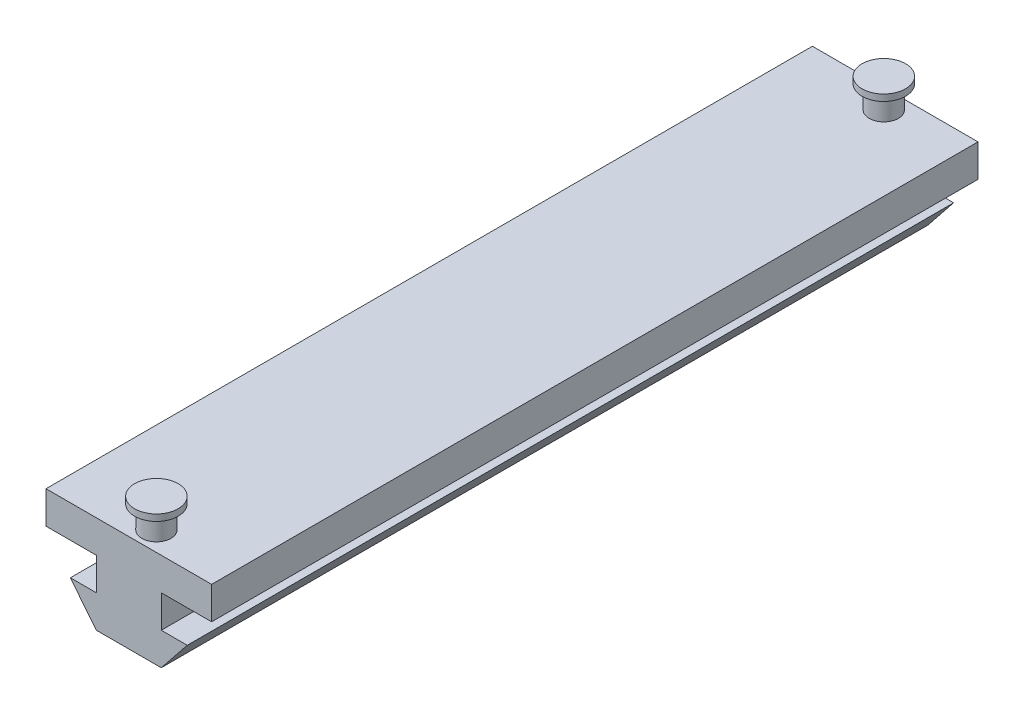
SolidWorks part; units mm, degrees
ref_plane "Front Plane" through (0, 0, 0) normal (0, 0, 1) x (1, 0, 0)
ref_plane "Top Plane" through (0, 0, 0) normal (0, 1, 0) x (1, 0, 0)
ref_plane "Right Plane" through (0, 0, 0) normal (1, 0, 0) x (0, 0, -1)
sketch "Sketch1" plane through (0, 0, 0) normal (0, 1, 0) x (1, 0, 0)
  line L1 (-12.75, -59) -> (12.75, -59)
  line L2 (-12.75, -59) -> (-12.75, 59)
  line L3 (-12.75, 59) -> (12.75, 59)
  line L4 (12.75, -59) -> (12.75, 59)
  line L5 (-12.75, -59) -> (12.75, 59) construction
  line L6 (-12.75, 59) -> (12.75, -59) construction
  point P0 (0, 0)
  dimension "D1" = 118
  dimension "D2" = 25.5
extrude "Boss-Extrude1" add sketch "Sketch1" along normal blind 5
sketch "Sketch2" plane through (0, 5, 0) normal (0, 1, 0) x (1, 0, 0)
  line L0 (12.75, 0) -> (-12.75, 0) construction
  line L1 (12.75, -59) -> (12.75, 59) construction
  line L2 (-12.75, 59) -> (-12.75, -59) construction
  circle A0 centre (1.25, 56) radius 2.25
  circle A1 centre (1.25, -56) radius 2.25
  dimension "D1" = 4.5
  dimension "D2" = 112
  dimension "D3" = 14
extrude "Boss-Extrude2" add sketch "Sketch2" along normal blind 3.5
sketch "Sketch3" plane through (0, 8.5, 0) normal (0, 1, 0) x (1, 0, 0)
  circle A0 centre (1.25, -56) radius 3.35
  circle A1 centre (1.25, 56) radius 3.35
  dimension "D1" = 6.7
extrude "Boss-Extrude3" add sketch "Sketch3" along normal blind 1
sketch "Sketch5" plane through (0, 0, 59) normal (0, 0, 1) x (1, 0, 0)
  line L1 (-12.75, 0) -> (12.75, 0) construction
  line L2 (-5, 0) -> (-5, -5)
  line L4 (-5, -10) -> (5, -10)
  line L6 (5, -5) -> (5, 0)
  line L7 (5, 0) -> (-5, 0)
  line L8 (0, 0) -> (0, -10) construction
  line L9 (-5, -5) -> (-9, -5)
  line L10 (-9, -5) -> (-5, -10)
  line L11 (5, -5) -> (9, -5)
  line L12 (9, -5) -> (5, -10)
  dimension "D1" = 5
  dimension "D2" = 5
  dimension "D3" = 4
  dimension "D4" = 10
extrude "Boss-Extrude5" add sketch "Sketch5" against normal blind 118
